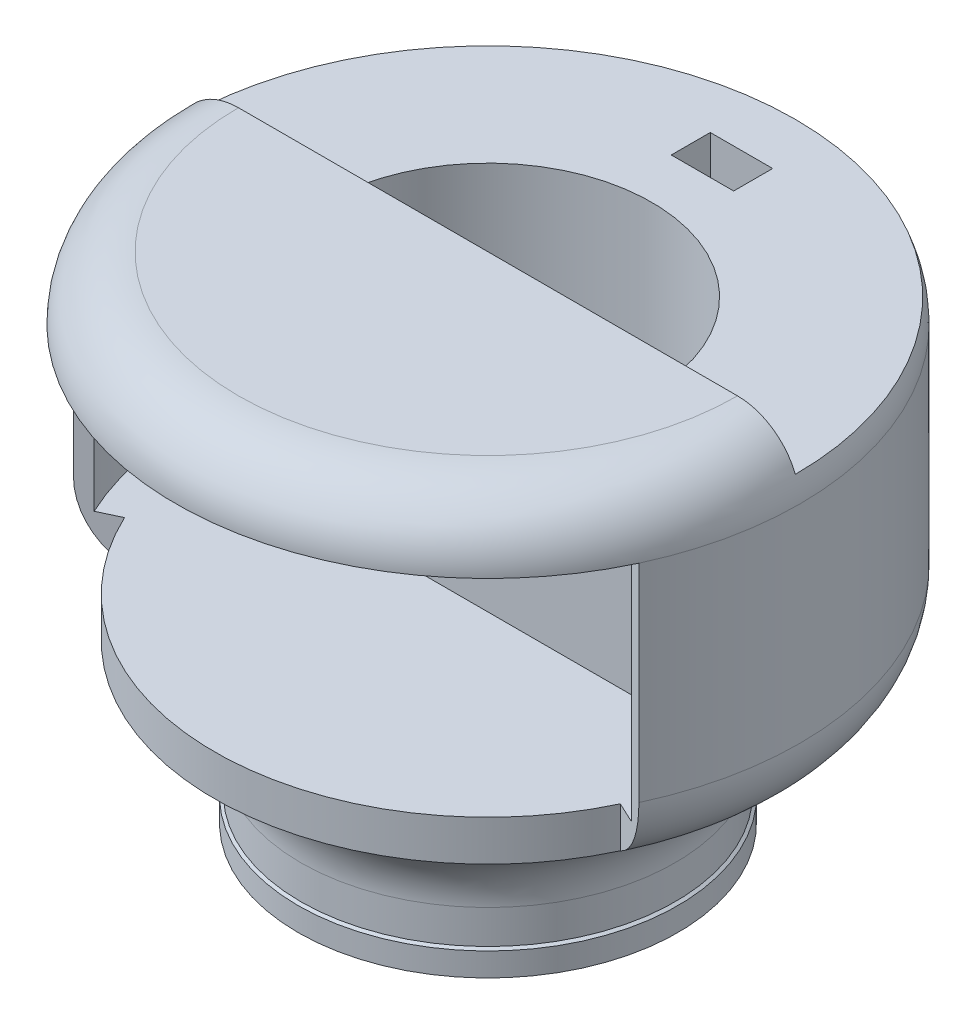
SolidWorks part; units mm, degrees
ref_plane "Front Plane" through (0, 0, 0) normal (0, 0, 1) x (1, 0, 0)
ref_plane "Top Plane" through (0, 0, 0) normal (0, 1, 0) x (1, 0, 0)
ref_plane "Right Plane" through (0, 0, 0) normal (1, 0, 0) x (0, 0, -1)
sketch "Sketch1" plane through (0, 0, 0) normal (0, 0, 1) x (1, 0, 0)
  line L0 (0, 0) -> (0, 90.2242) construction
  line L28 (0, 63.4279) -> (32, 63.4279)
  line L29 (40, 55.4279) -> (40, 28.8468)
  line L30 (22.5, 0) -> (24.35, 0)
  line L31 (24.35, 0) -> (24.35, 3)
  line L32 (24.35, 3) -> (24, 3.25)
  line L33 (24, 3.25) -> (24, 7.5811)
  line L34 (28.5399, 15.9588) -> (35.4601, 20.4691)
  line L35 (0, 13) -> (22, 13)
  line L36 (22.5, 12.5) -> (22.5, 0)
  line L37 (0, 13) -> (0, 63.4279)
  arc A0 (22, 13) -> (22.5, 12.5) centre (22, 12.5) cw
  arc A1 (24, 7.5811) -> (28.5399, 15.9588) centre (34, 7.5811) cw
  arc A2 (35.4601, 20.4691) -> (40, 28.8468) centre (30, 28.8468) ccw
  arc A3 (32, 63.4279) -> (40, 55.4279) centre (32, 55.4279) cw
  point P11 (22.9, 63.4279)
  point P18 (22.5, 13)
  point P21 (24, 13)
  point P24 (40, 23.4279)
  point P27 (40, 63.4279)
  point P28 (28.5604, 23.4279)
  point P31 (22.5, 17)
  dimension "D8" = 9.75
  dimension "D9" = 0.5
  dimension "D4" = 1.85
  dimension "D1" = 22.5
  dimension "D10" = 10
  dimension "D11" = 10
  dimension "D12" = 8
  dimension "D2" = 40
  dimension "D3" = 40
  dimension "D5" = 1.5
  dimension "D6" = 3
  dimension "D7" = 13
revolve "Revolve1" add sketch "Sketch1" angle 360 about L0
ref_plane "Plane1" through (0, 13, 0) normal (0, -1, 0) x (-1, 0, 0)
sketch "Sketch18" plane through (0, 0, 0) normal (0, 0, 1) x (1, 0, 0)
  line L0 (0, 0) -> (0, 101.5813) construction
  line L1 (-24.35, 0) -> (24.35, 0) construction
sketch "Sketch3" plane through (0, 0, 0) normal (0, 0, 1) x (1, 0, 0)
  point P0 (1.2404, 19.1989)
ref_point "Point1"
ref_plane "Plane2" through (0, 0, 22.9) normal (0, 0, 1) x (1, 0, 0)
ref_plane "Plane3" through (0, 0, 40) normal (0, 0, 1) x (1, 0, 0)
ref_plane "Plane4" through (0, 55.4279, 0) normal (0, 1, 0) x (1, 0, 0)
sketch "Sketch9" plane through (0, 55.4279, 0) normal (0, 1, 0) x (1, 0, 0)
  circle A7 centre (0, 0) radius 38
  circle A8 centre (0, 0) radius 40 construction
  circle A9 centre (0, 0) radius 23
  dimension "D1" = 2
  dimension "D2" = 46
ref_plane "Plane5" through (0, 13, 0) normal (0, -1, 0) x (-1, 0, 0)
sketch "Sketch11" plane through (0, 13, 0) normal (0, -1, 0) x (-1, 0, 0)
  line L0 (-21, 0) -> (21, 0)
  arc A1 (-21, 0) -> (21, 0) centre (0, 0) cw
  dimension "D1" = 42
extrude "Cut-Extrude3" cut sketch "Sketch11" against normal blind 60
ref_plane "Plane6" through (0, 0, -40) normal (0, 0, -1) x (-1, 0, 0)
extrude "Cut-Extrude5" cut sketch "Sketch9" against normal blind 30 and the other way blind 2
sketch "Sketch19" plane through (0, 0, 0) normal (1, 0, 0) x (0, 0, -1)
  line L0 (-47.0647, 55.4279) -> (-35.0647, 55.4279)
  line L1 (31.2976, 55.4279) -> (-31.2976, 55.4279) construction
  line L2 (-35.0647, 55.4279) -> (-35.0647, 18.9279)
  line L3 (-35.0647, 18.9279) -> (-47.0647, 18.9279)
  line L4 (-47.0647, 18.9279) -> (-47.0647, 55.4279)
  dimension "D1" = 12
  dimension "D2" = 36.5
revolve "Cut-Revolve2" cut sketch "Sketch19" angle 65 about L0 other way angle 65
ref_plane "Plane7" through (0, 0, 22.5) normal (0, 0, -1) x (-1, 0, 0)
sketch "Sketch21" plane through (0, 0, 22.5) normal (0, 0, -1) x (-1, 0, 0)
  line L0 (0, 0) -> (0, 101.5813) construction
  line L1 (-1.625, 4) -> (1.625, 4)
  line L2 (-1.625, 4) -> (-1.625, 0)
  line L3 (-1.625, 0) -> (1.625, 0)
  line L4 (1.625, 4) -> (1.625, 0)
  line L5 (-1.625, 4) -> (1.625, 0) construction
  line L6 (-1.625, 0) -> (1.625, 4) construction
  line L7 (-22.5, 0) -> (22.5, 0) construction
  point P0 (0, 2)
  dimension "D1" = 4
  dimension "D2" = 3.25
extrude "Boss-Extrude3" add sketch "Sketch21" along normal blind 1.35
pattern_circular "CirPattern1" count 5 over 360 about axis through (0, 0, 0) along (0, -1, 0) of "Boss-Extrude3"
ref_plane "Plane8" through (0, 20.4691, 0) normal (0, 1, 0) x (1, 0, 0)
sketch "Sketch22" plane through (0, 63.4279, 0) normal (0, 1, 0) x (1, 0, 0)
  line L0 (-40, 0) -> (40, 0)
  arc A0 (-40, 0) -> (40, 0) centre (0, 0) cw
  arc A1 (36.2523, -16.9047) -> (-36.2523, -16.9047) centre (0, 0) ccw construction
extrude "Cut-Extrude9" cut sketch "Sketch22" against normal blind 5
sketch "Sketch23" plane through (0, 0, -40) normal (0, 0, -1) x (-1, 0, 0)
  line L0 (0, 0) -> (0, 101.5813) construction
  line L1 (31.2976, 55.4279) -> (-31.2976, 55.4279) construction
  circle A0 centre (0, 42.1379) radius 10.5
  dimension "D1" = 21
  dimension "D2" = 13.29
extrude "Cut-Extrude10" cut sketch "Sketch23" against normal blind 10
sketch "Sketch24" plane through (0, 58.4279, 0) normal (0, 1, 0) x (1, 0, 0)
  line L1 (-7.5, 34) -> (7.5, 34)
  line L2 (-7.5, 34) -> (-7.5, 26)
  line L3 (-7.5, 26) -> (7.5, 26)
  line L4 (7.5, 34) -> (7.5, 26)
  line L5 (-7.5, 34) -> (7.5, 26) construction
  line L6 (-7.5, 26) -> (7.5, 34) construction
  arc A0 (39.4162, 0) -> (-39.4162, 0) centre (0, 0) ccw construction
  point P0 (0, 30)
  dimension "D1" = 30
  dimension "D2" = 8
  dimension "D3" = 15
extrude "Boss-Extrude4" add sketch "Sketch24" against normal blind 8
sketch "Sketch26" plane through (0, 58.4279, 0) normal (0, 1, 0) x (1, 0, 0)
  line L1 (-4, 32.5) -> (4, 32.5)
  line L2 (-4, 32.5) -> (-4, 27.5)
  line L3 (-4, 27.5) -> (4, 27.5)
  line L4 (4, 32.5) -> (4, 27.5)
  line L5 (-4, 32.5) -> (4, 27.5) construction
  line L6 (-4, 27.5) -> (4, 32.5) construction
  arc A0 (39.4162, 0) -> (-39.4162, 0) centre (0, 0) ccw construction
  point P0 (0, 30)
  dimension "D1" = 30
  dimension "D2" = 5
  dimension "D3" = 8
extrude "Cut-Extrude11" cut sketch "Sketch26" against normal blind 10
sketch "Sketch27" plane through (7.5, 0, 0) normal (1, 0, 0) x (0, 0, -1)
  line L0 (34, 50.4279) -> (34, 57.4279) construction
  line L1 (28, 56.4279) -> (32, 56.4279)
  line L2 (28, 56.4279) -> (28, 51.4279)
  line L3 (28, 51.4279) -> (32, 51.4279)
  line L4 (32, 56.4279) -> (32, 51.4279)
  line L5 (28, 56.4279) -> (32, 51.4279) construction
  line L6 (28, 51.4279) -> (32, 56.4279) construction
  line L7 (26, 50.4279) -> (26, 57.4279) construction
  line L8 (26, 50.4279) -> (34, 50.4279) construction
  point P0 (30, 53.9279)
  dimension "D1" = 8
  dimension "D2" = 3.5
  dimension "D3" = 5
  dimension "D4" = 4
extrude "Cut-Extrude12" cut sketch "Sketch27" against normal blind 5
ref_plane "Plane9" through (-39.4162, 58.4279, 0) normal (0.375, 0.927, 0) x (0.927, -0.375, 0)
ref_plane "Plane10" through (0, 58.4279, 0) normal (0, 1, 0) x (1, 0, 0)
sketch3d "3DSketch1"
  line L2 (31.7794, 25.4279, 14.819) -> (34.2611, 25.4279, 15.9762)
  line L3 (-34.2611, 25.4279, 15.9762) -> (-31.7794, 25.4279, 14.819)
  line L4 (31.7794, 25.4279, 14.819) -> (34.2611, 25.4279, 15.9762)
  line L5 (-34.2611, 25.4279, 15.9762) -> (-31.7794, 25.4279, 14.819)
  arc A2 (34.2611, 25.4279, 15.9762) -> (-34.2611, 25.4279, 15.9762) centre (0, 25.4279, 2) ccw
  arc A3 (-31.7794, 25.4279, 14.819) -> (31.7794, 25.4279, 14.819) centre (0, 25.4279, 0) ccw
  arc A4 (34.2611, 25.4279, 15.9762) -> (-34.2611, 25.4279, 15.9762) centre (0, 25.4279, 2) ccw
  arc A5 (-31.7794, 25.4279, 14.819) -> (31.7794, 25.4279, 14.819) centre (0, 25.4279, 0) ccw
  point P6 (0, 62.43, 2)
  point P10 (0, 60.4926, 0)
  point P12 (0, 62.43, 2)
  point P13 (0, 60.4926, 0)
  dimension "D1" = 0
sketch "Sketch28" plane through (0, 55.4279, 0) normal (0, 1, 0) x (1, 0, 0)
  line L0 (-22.9129, -2) -> (22.9129, -2)
  arc A0 (-22.9129, -2) -> (22.9129, -2) centre (0, 0) ccw
  dimension "D1" = 46
  dimension "D2" = 2
extrude "Cut-Extrude14" cut sketch "Sketch28" against normal blind 30 and the other way blind 2
